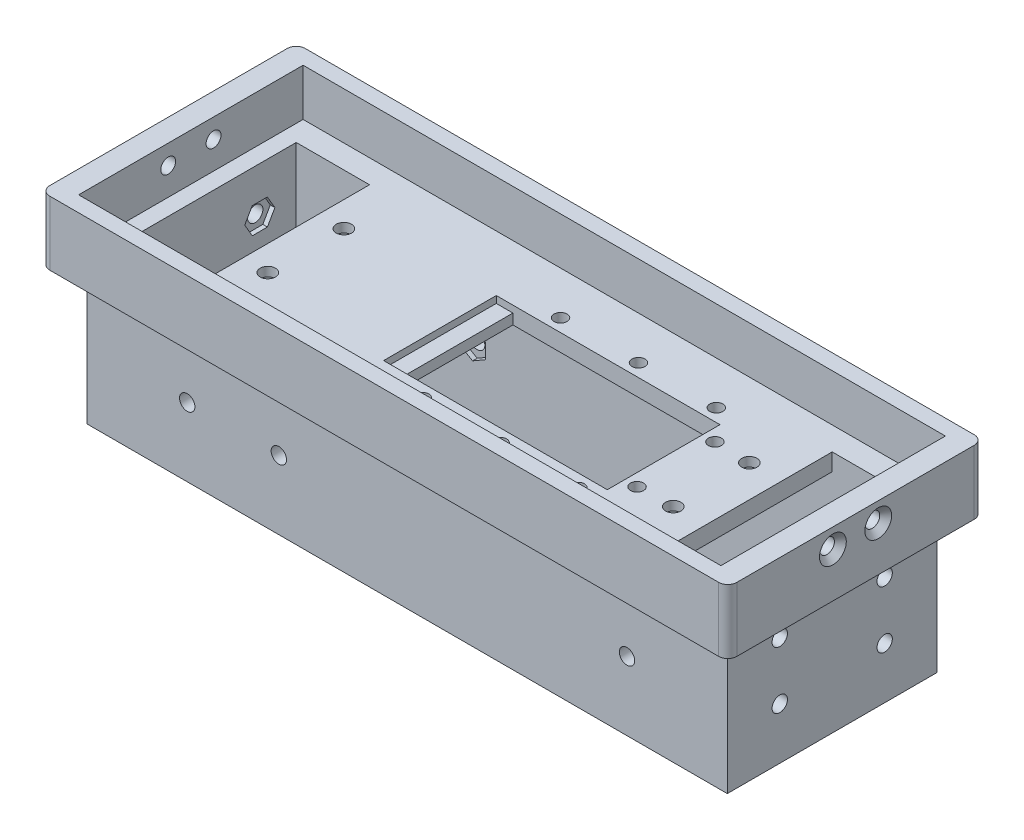
SolidWorks part; units mm, degrees
ref_plane "前视基准面" through (0, 0, 0) normal (0, 0, 1) x (1, 0, 0)
ref_plane "上视基准面" through (0, 0, 0) normal (0, 1, 0) x (1, 0, 0)
ref_plane "右视基准面" through (0, 0, 0) normal (1, 0, 0) x (0, 0, -1)
sketch "草图1" plane through (0, 0, 0) normal (0, 1, 0) x (1, 0, 0)
  line L1 (-75, 25.9) -> (75, 25.9)
  line L2 (-75, 25.9) -> (-75, -25.9)
  line L3 (-75, -25.9) -> (75, -25.9)
  line L4 (75, 25.9) -> (75, -25.9)
  line L5 (-75, 25.9) -> (75, -25.9) construction
  line L6 (-75, -25.9) -> (75, 25.9) construction
  line L7 (-70.1, 21) -> (70.1, 21)
  line L8 (-70.1, 21) -> (-70.1, -21)
  line L9 (-70.1, -21) -> (70.1, -21)
  line L10 (70.1, 21) -> (70.1, -21)
  line L11 (-70.1, 21) -> (70.1, -21) construction
  line L12 (-70.1, -21) -> (70.1, 21) construction
  point P0 (0, 0)
  point P5 (0, 0)
  dimension "D1" = 150
  dimension "D2" = 51.8
  dimension "D3" = 4.9
  dimension "D4" = 4.9
extrude "凸台-拉伸1" add sketch "草图1" along normal blind 12
sketch "草图2" plane through (0, 0, 0) normal (0, 1, 0) x (1, 0, 0)
  line L1 (70.1, 21) -> (-70.1, 21)
  line L2 (70.1, 21) -> (70.1, -21)
  line L3 (70.1, -21) -> (-70.1, -21)
  line L4 (-70.1, 21) -> (-70.1, -21)
  line L5 (70.1, 21) -> (-70.1, -21) construction
  line L6 (70.1, -21) -> (-70.1, 21) construction
  point P0 (0, 0)
extrude "凸台-拉伸2" add sketch "草图2" along normal blind 2.25
ref_plane "基准面1" through (0, 2.25, 0) normal (0, -1, 0) x (-1, 0, 0)
sketch "草图3" plane through (0, 2.25, 0) normal (0, 1, 0) x (1, 0, 0)
  line L1 (-12.1, 12.3) -> (33.1, 12.3)
  line L2 (-12.1, 12.3) -> (-12.1, -12.3)
  line L3 (-12.1, -12.3) -> (33.1, -12.3)
  line L4 (33.1, 12.3) -> (33.1, -12.3)
  dimension "D1" = 12.1
  dimension "D2" = 12.3
  dimension "D3" = 12.3
  dimension "D4" = 45.2
extrude "切除-拉伸1" cut sketch "草图3" against normal through all contours L2 L3 L4 L1
ref_plane "基准面2" through (0, 0, 0) normal (0, -1, 0) x (-1, 0, 0)
ref_plane "基准面4" through (0, 2.25, 0) normal (0, 1, 0) x (1, 0, 0)
sketch "草图8" plane through (0, 2.25, 0) normal (0, 1, 0) x (1, 0, 0)
  line L0 (-12.1, -12.3) -> (33.1, -12.3)
  line L1 (33.1, -12.3) -> (33.1, 12.3)
  line L2 (33.1, 12.3) -> (-70.1, 12.3)
  line L3 (-70.1, 21) -> (-70.1, -21) construction
  line L4 (-70.1, 12.3) -> (-70.1, 21)
  line L5 (-70.1, 21) -> (70.1, 21)
  line L6 (70.1, 21) -> (70.1, -21)
  line L7 (70.1, -21) -> (-70.1, -21)
  line L8 (-70.1, -21) -> (-70.1, -12.3)
  line L9 (-70.1, 21) -> (-70.1, -21) construction
  line L10 (-70.1, -12.3) -> (-12.1, -12.3)
extrude "凸台-拉伸5" add sketch "草图8" along normal blind 1.5
sketch "草图9" plane through (0, 2.25, 0) normal (0, 1, 0) x (1, 0, 0)
  line L0 (-15.7293, 12.3) -> (-15.7293, -12.3)
  line L1 (-70.1, 12.3) -> (-12.1, 12.3) construction
  line L2 (-12.1, -12.3) -> (-70.1, -12.3) construction
  line L3 (-15.7293, -12.3) -> (-70.1, -12.3)
  line L4 (-70.1, -12.3) -> (-70.1, 12.3)
  line L5 (-70.1, 12.3) -> (-15.7293, 12.3)
extrude "凸台-拉伸6" add sketch "草图9" along normal blind 1.5
ref_plane "基准面5" through (0, 3.75, 0) normal (0, 1, 0) x (1, 0, 0)
sketch "草图10" plane through (0, 3.75, 0) normal (0, 1, 0) x (1, 0, 0)
  circle A0 centre (-4.5, 15.1) radius 1.425
  circle A1 centre (12.5, 15.1) radius 1.425
  circle A2 centre (29.5, 15.1) radius 1.425
  dimension "D1" = 2.85
  dimension "D2" = 2.85
  dimension "D3" = 2.85
extrude "Screw_holes_for_connectng_the_servo" cut sketch "草图10" against normal through all
mirror "Screw_holes_for_connectng_the_servo(2)" about plane through (0, 0, 0) normal (0, 0, 1) of "Screw_holes_for_connectng_the_servo"
ref_plane "基准面7" through (0, 0, 0) normal (0, -1, 0) x (-1, 0, 0)
sketch "草图12" plane through (0, 0, 0) normal (0, -1, 0) x (-1, 0, 0)
  line L0 (75, 25.9) -> (75, -25.9) construction
  line L1 (-70, 22.9) -> (70, 22.9)
  line L2 (-70, 22.9) -> (-70, -22.9)
  line L3 (-70, -22.9) -> (70, -22.9)
  line L4 (70, 22.9) -> (70, -22.9)
  line L5 (-70, 22.9) -> (70, -22.9) construction
  line L6 (-70, -22.9) -> (70, 22.9) construction
  line L7 (-75, 25.9) -> (75, 25.9) construction
  line L9 (-66.5, 19.4) -> (66.5, 19.4)
  line L10 (-66.5, 19.4) -> (-66.5, -19.4)
  line L11 (-66.5, -19.4) -> (66.5, -19.4)
  line L12 (66.5, 19.4) -> (66.5, -19.4)
  line L13 (-66.5, 19.4) -> (66.5, -19.4) construction
  line L14 (-66.5, -19.4) -> (66.5, 19.4) construction
  point P0 (0, 0)
  point P10 (0, 0)
  dimension "D1" = 5
  dimension "D2" = 3
  dimension "D3" = 3.5
  dimension "D4" = 3.5
extrude "凸台-拉伸9" add sketch "草图12" along normal blind 25
ref_plane "基准面8" through (0, 0, 0) normal (0, -1, 0) x (-1, 0, 0)
sketch "草图16" plane through (0, 0, 0) normal (0, -1, 0) x (-1, 0, 0)
  line L0 (-66.5, 19.4) -> (-66.5, -19.9)
  line L1 (-66.5, 19.4) -> (-66.5, -19.4) construction
  line L2 (-66.5, 19.4) -> (-66.5, -19.4) construction
  line L3 (-66.5, -19.9) -> (-50.5, -19.4)
  line L4 (-66.5, -19.4) -> (66.5, -19.4) construction
  line L5 (-50.5, -19.4) -> (-50.5, 19.4)
  line L6 (66.5, 19.4) -> (-66.5, 19.4) construction
  line L7 (-50.5, 19.4) -> (-66.5, 19.4)
  line L8 (66.5, 19.4) -> (50.5, 19.4)
  line L9 (50.5, 19.4) -> (50.5, -19.4)
  line L10 (50.5, -19.4) -> (66.5, -19.4)
  line L11 (66.5, -19.4) -> (66.5, 19.4)
  dimension "D1" = 16
  dimension "D2" = 16
extrude "切除-拉伸4" cut sketch "草图16" against normal through all
ref_plane "基准面9" through (75, 0, 0) normal (1, 0, 0) x (0, 0, -1)
sketch "草图18" plane through (75, 0, 0) normal (1, 0, 0) x (0, 0, -1)
  line L0 (0, 12) -> (0, 5.5)
  line L1 (-25.9, 12) -> (25.9, 12) construction
  line L2 (0, 8.75) -> (-4.95, 8.75)
  line L3 (0, 8.75) -> (4.95, 8.75)
  circle A0 centre (4.95, 8.75) radius 1.6
  circle A1 centre (-4.95, 8.75) radius 1.6
  dimension "D1" = 4.95
  dimension "D2" = 4.95
extrude "切除-拉伸5" [suppressed] cut sketch "草图18" against normal through all contours A1 | A0
ref_plane "基准面11" through (0, 0, 25.9) normal (0, 0, 1) x (1, 0, 0)
ref_plane "基准面12" through (0, 0, -25.9) normal (0, 0, -1) x (-1, 0, 0)
sketch "草图21" plane through (0, 0, 25.9) normal (0, 0, 1) x (1, 0, 0)
  line L0 (75, 12) -> (75, 5.5)
  line L1 (75, 12) -> (75, 0) construction
  line L2 (75, 5.5) -> (75, 8.75)
  line L3 (75, 8.75) -> (72, 8.75)
  line L4 (72, 8.75) -> (62, 8.75)
  line L5 (62, 8.75) -> (52, 8.75)
  line L6 (52, 8.75) -> (42, 8.75)
  line L7 (42, 12) -> (42, 5.5)
  line L8 (-75, 12) -> (75, 12) construction
  line L9 (42, 5.5) -> (52, 12)
  line L10 (52, 12) -> (52, 5.5)
  line L11 (52, 5.5) -> (62, 12)
  line L12 (62, 12) -> (62, 5.5)
  line L13 (62, 5.5) -> (72, 5.5)
  line L14 (72, 5.5) -> (72, 12)
  line L15 (72, 12) -> (62, 5.5)
  circle A1 centre (57, 8.75) radius 1.6
  circle A2 centre (67, 8.75) radius 1.6
sketch "草图22" plane through (0, 0, -25.9) normal (0, 0, -1) x (-1, 0, 0)
  line L0 (75, 12) -> (75, 5.5)
  line L1 (75, 12) -> (75, 0) construction
  line L2 (75, 5.5) -> (75, 8.75)
  line L3 (75, 8.75) -> (72, 8.75)
  line L4 (72, 8.75) -> (62, 8.75)
  line L5 (62, 8.75) -> (52, 8.75)
  line L7 (72, 12) -> (72, 5.5)
  line L8 (-75, 12) -> (75, 12) construction
  line L9 (72, 5.5) -> (62, 12)
  line L10 (62, 12) -> (62, 5.5)
  line L11 (62, 5.5) -> (52, 12)
  circle A4 centre (57, 8.75) radius 1.6
  circle A5 centre (67, 8.75) radius 1.6
extrude "切除-拉伸12" [suppressed] cut sketch "草图21" against normal blind 5 contours A1 | A2
extrude "切除-拉伸13" [suppressed] cut sketch "草图22" along normal blind 2 and the other way blind 5 contours A4 | A5
ref_plane "基准面13" through (70, 0, 0) normal (1, 0, 0) x (0, 0, -1)
sketch "草图23" plane through (70, 0, 0) normal (1, 0, 0) x (0, 0, -1)
  line L0 (22.9, -25) -> (-22.9, 0)
  line L1 (-22.9, 0) -> (-22.9, -25)
  line L2 (-22.9, -25) -> (22.9, 0)
  line L3 (22.9, 0) -> (22.9, -12.5)
  line L4 (22.9, -25) -> (22.9, 0) construction
  line L5 (22.9, -12.5) -> (-22.9, -12.5)
  line L6 (-22.9, -12.5) -> (0, 0)
  line L7 (0, 0) -> (0, -25)
  line L8 (22.9, -25) -> (-22.9, -25) construction
  line L9 (0, -25) -> (22.9, -12.5)
  line L10 (22.9, -12.5) -> (0, 0)
  line L11 (-22.9, -12.5) -> (0, -25)
  circle A0 centre (-11.45, -6.25) radius 1.675
  circle A1 centre (11.45, -6.25) radius 1.675
  circle A2 centre (11.45, -18.75) radius 1.675
  circle A3 centre (-11.45, -18.75) radius 1.675
  dimension "D1" = 3.35
  dimension "D2" = 3.35
  dimension "D3" = 3.35
  dimension "D4" = 3.35
extrude "切除-拉伸14" cut sketch "草图23" against normal through all contours A0 | A3 | A1 | A2
ref_plane "基准面14" through (0, 0, -22.9) normal (0, 0, -1) x (-1, 0, 0)
sketch "草图24" plane through (0, 0, -22.9) normal (0, 0, -1) x (-1, 0, 0)
  line L0 (70, -12.5) -> (24, -12.5)
  line L1 (70, -25) -> (70, 0) construction
  line L2 (24, -12.5) -> (-24, -12.5)
  line L3 (-24, -12.5) -> (-70, -12.5)
  line L4 (-70, 13.75) -> (-70, -13.75) construction
  line L6 (70, -25) -> (-70, -25) construction
  line L7 (-70, -25) -> (-24, 0)
  line L8 (-75, 0) -> (75, 0) construction
  line L9 (-24, 0) -> (24, -25)
  line L10 (24, -25) -> (70, 0)
  circle A2 centre (47, -12.5) radius 2.075
  circle A3 centre (-47, -12.5) radius 2.075
  dimension "D1" = 4.15
  dimension "D2" = 4.15
sketch "草图26" plane through (0, 3.75, 0) normal (0, 1, 0) x (1, 0, 0)
  line L0 (-70.1, -21) -> (-70.1, 21)
  dimension "D1" = 42
ref_plane "基准面15" through (0, 0, -21) normal (0, 0, 1) x (1, 0, 0)
ref_plane "基准面16" through (0, 0, 21) normal (0, 0, -1) x (-1, 0, 0)
ref_plane "基准面17" through (-70.1, 0, 0) normal (1, 0, 0) x (0, 0, -1)
ref_plane "基准面18" through (50.5, 0, 0) normal (1, 0, 0) x (0, 0, -1)
ref_plane "基准面19" through (0, 0, 0) normal (0, -1, 0) x (-1, 0, 0)
sketch "草图49" plane through (0, -25, 0) normal (0, -1, 0) x (-1, 0, 0)
  line L1 (66.5, -19.4) -> (-66.5, -19.4)
  line L2 (66.5, -19.4) -> (66.5, 19.4)
  line L3 (66.5, 19.4) -> (-66.5, 19.4)
  line L4 (-66.5, -19.4) -> (-66.5, 19.4)
  line L5 (70, -22.9) -> (-70, -22.9)
  line L6 (70, -22.9) -> (70, 22.9)
  line L7 (70, 22.9) -> (-70, 22.9)
  line L8 (-70, -22.9) -> (-70, 22.9)
extrude "凸台-拉伸13" add sketch "草图49" along normal blind 5
sketch "草图53" plane through (70, 0, 0) normal (1, 0, 0) x (0, 0, -1)
  line L1 (-22.9, 0) -> (22.9, 0)
  line L2 (-22.9, 0) -> (-22.9, -30)
  line L3 (-22.9, -30) -> (22.9, -30)
  line L4 (22.9, 0) -> (22.9, -30)
  circle A0 centre (-11.45, -6.25) radius 1.6
  circle A1 centre (-11.45, -18.75) radius 1.6
  circle A2 centre (11.45, -18.75) radius 1.6
  circle A3 centre (11.45, -6.25) radius 1.6
extrude "切除-拉伸19" cut sketch "草图53" against normal blind 0.1
mirror "镜向7" about plane through (0, 0, 0) normal (1, 0, 0) of "切除-拉伸19"
ref_plane "基准面20" through (0, 0, -22.9) normal (0, 0, -1) x (-1, 0, 0)
sketch "草图59" plane through (0, 0, -22.9) normal (0, 0, -1) x (-1, 0, 0)
  line L0 (-69.9, 0) -> (-69.9, -15)
  line L1 (-69.9, -15) -> (69.9, -15)
  line L2 (-69.9, -30) -> (-69.9, 0) construction
  line L3 (-69.9, -15) -> (-48, -15)
  line L4 (69.9, 0) -> (69.9, -15)
  line L6 (69.9, -30) -> (69.9, 0) construction
  line L7 (69.9, -15) -> (48, -15)
  line L8 (48, -15) -> (28, -15)
  circle A0 centre (-48, -15) radius 1.675
  circle A1 centre (28, -15) radius 1.675
  circle A2 centre (48, -15) radius 1.675
  point P2 (0, -15)
  dimension "D1" = 3.35
  dimension "D2" = 3.35
  dimension "D3" = 3.35
  dimension "D4" = 28
  dimension "D5" = 20
  dimension "D6" = 48
extrude "切除-拉伸20" cut sketch "草图59" against normal through all contours A0 | A1 | A2
ref_plane "基准面22" through (-50.5, 0, 0) normal (-1, 0, 0) x (0, 0, 1)
ref_plane "基准面23" through (0, 3.75, 0) normal (0, 1, 0) x (1, 0, 0)
sketch "草图66" plane through (0, 3.75, 0) normal (0, 1, 0) x (1, 0, 0)
  line L0 (29.5, -15.1) -> (43.5, -15.1)
  line L1 (33.1, -12.3) -> (43.5, -12.3)
  line L2 (43.5, -12.3) -> (43.5, -8.3)
  line L3 (33.1, 12.3) -> (43.5, 12.3)
  line L4 (43.5, 12.3) -> (43.5, 8.3)
  line L5 (0, 0) -> (43.5, 0)
  line L6 (0, 0) -> (-45, 0)
  line L7 (-45, 0) -> (-45, 8.3)
  line L8 (-45, 0) -> (-45, -8.3)
  circle A0 centre (43.5, -8.3) radius 1.675
  circle A1 centre (43.5, 8.3) radius 1.675
  circle A2 centre (-45, 8.3) radius 1.675
  circle A3 centre (-45, -8.3) radius 1.675
  dimension "D4" = 43.5
  dimension "D1" = 14
  dimension "D2" = 4
  dimension "D3" = 4
  dimension "D5" = 45
  dimension "D6" = 8.3
extrude "切除-拉伸21" cut sketch "草图66" against normal blind 20 contours A2 | A3 | A1 | A0
ref_plane "基准面24" through (0, 0, -25.9) normal (0, 0, -1) x (-1, 0, 0)
sketch "草图67" plane through (0, 0, -25.9) normal (0, 0, -1) x (-1, 0, 0)
  line L1 (-75, 12) -> (75, 12)
  line L2 (-75, 12) -> (-75, 0)
  line L3 (-75, 0) -> (75, 0)
  line L4 (75, 12) -> (75, 0)
extrude "凸台-拉伸15" add sketch "草图67" along normal blind 2
mirror "镜向10" about plane through (0, 0, 0) normal (0, 0, 1) of "凸台-拉伸15"
sketch "草图69" plane through (0, 3.75, 0) normal (0, 1, 0) x (1, 0, 0)
  line L0 (29.5, 15.1) -> (35.8, 15.1)
  line L2 (29.5, -15.1) -> (35.8, -15.1)
  circle A0 centre (35.8, 8.5) radius 1.425
  circle A1 centre (35.8, -8.5) radius 1.425
extrude "切除-拉伸22" cut sketch "草图69" against normal up to next contours A0 | A1 region at (35.8, 3.75, -8.5) region at (35.8, 3.75, 8.5)
sketch "草图71" plane through (0, 0, 0) normal (0, -1, 0) x (-1, 0, 0)
  line L0 (-40.65, -6.6546) -> (-40.65, -2.614)
  line L1 (-43.5, -5.0091) -> (-46.35, -6.6546)
  line L2 (-46.35, -6.6546) -> (-46.35, -9.9454)
  line L3 (-46.35, -9.9454) -> (-43.5, -11.5909)
  line L4 (-43.5, -11.5909) -> (-40.65, -9.9454)
  line L5 (-40.65, -9.9454) -> (-40.65, -6.6546)
  line L6 (-40.65, -6.6546) -> (-43.5, -5.0091)
  line L7 (-43.5, 11.626) -> (-46.3804, 9.963)
  line L8 (-46.3804, 9.963) -> (-46.3804, 6.637)
  line L9 (-46.3804, 6.637) -> (-43.5, 4.974)
  line L10 (-43.5, 4.974) -> (-40.6196, 6.637)
  line L11 (-40.6196, 6.637) -> (-40.6196, 9.963)
  line L12 (-40.6196, 9.963) -> (-43.5, 11.626)
  line L13 (45.0917, 11.626) -> (42.1654, 10.0425)
  line L14 (42.1654, 10.0425) -> (42.0737, 6.7164)
  line L15 (42.0737, 6.7164) -> (44.9083, 4.974)
  line L16 (44.9083, 4.974) -> (47.8346, 6.5575)
  line L17 (47.8346, 6.5575) -> (47.9263, 9.8836)
  line L18 (47.9263, 9.8836) -> (45.0917, 11.626)
  line L19 (45.0917, -4.9685) -> (42.1607, -6.5548)
  line L20 (42.1607, -6.5548) -> (42.069, -9.8863)
  line L21 (42.069, -9.8863) -> (44.9083, -11.6315)
  line L22 (44.9083, -11.6315) -> (47.8393, -10.0452)
  line L23 (47.8393, -10.0452) -> (47.931, -6.7137)
  line L24 (47.931, -6.7137) -> (45.0917, -4.9685)
  line L26 (-40.65, -9.9454) -> (-40.65, -13.9454)
  circle A0 centre (-43.5, -8.3) radius 2.85 construction
  circle A1 centre (-43.5, 8.3) radius 2.8804 construction
  circle A2 centre (45, 8.3) radius 2.8815 construction
  circle A3 centre (45, -8.3) radius 2.8863 construction
  circle A4 centre (-43.5, -8.3) radius 1.675
  circle A5 centre (-43.5, 8.3) radius 1.675
  circle A6 centre (45, -8.3) radius 1.675
  circle A7 centre (45, 8.3) radius 1.675
  point P28 (42.1196, 8.3795)
  circle M12 centre (-43.5, -8.3) radius 1.675
  dimension "D4" = 5.7
  dimension "D1" = 5.7609
  dimension "D2" = 5.7631
  dimension "D3" = 5.7725
sketch "草图74" plane through (0, 0, 0) normal (0, -1, 0) x (-1, 0, 0)
  line L1 (45, -5.0091) -> (42.15, -6.6546)
  line L2 (42.15, -6.6546) -> (42.15, -9.9454)
  line L3 (42.15, -9.9454) -> (45, -11.5909)
  line L4 (45, -11.5909) -> (47.85, -9.9454)
  line L5 (47.85, -9.9454) -> (47.85, -6.6546)
  line L6 (47.85, -6.6546) -> (45, -5.0091)
  line L8 (40, -5.4132) -> (40, -11.1868)
  line L11 (50, -11.1868) -> (50, -5.4132)
  line L13 (45, -14.0735) -> (50, -11.1868) [skipped]
  line L14 (50, -5.4132) -> (45, -2.5265) [skipped]
  line L15 (40, -11.1868) -> (45, -14.0735) [skipped]
  line L16 (45, -2.5265) -> (40, -5.4132) [skipped]
  circle A0 centre (45, -8.3) radius 2.85 construction
  circle A1 centre (45, -8.3) radius 5 construction
  circle A2 centre (45, -8.3) radius 1.675
  circle M30 centre (45, -8.3) radius 1.675
  dimension "D1" = 5.7
  dimension "D2" = 10
sketch "草图77" plane through (0, 0, -21) normal (0, 0, 1) x (1, 0, 0)
  line L0 (-70.1, 12) -> (-70.1, 3.75)
  line L1 (-70.1, 3.75) -> (70.1, 3.75)
  line L2 (70.1, 3.75) -> (70.1, 12)
  line L3 (70.1, 12) -> (-70.1, 12)
extrude "切除-拉伸23" cut sketch "草图77" against normal blind 3.5
mirror "镜向13" about plane through (0, 0, 0) normal (0, 0, 1) of "切除-拉伸23"
chamfer "倒角1" [suppressed] distance 1.3 angle 45
chamfer "倒角2" [suppressed] distance 1.3 angle 45
sketch "草图82" plane through (66.5, 0, 0) normal (-1, 0, 0) x (0, 0, 1)
  line L1 (-9.8171, -9.1072) -> (-8.1591, -6.2645)
  line L2 (-8.1591, -6.2645) -> (-9.792, -3.4073)
  line L3 (-9.792, -3.4073) -> (-13.0829, -3.3928)
  line L4 (-13.0829, -3.3928) -> (-14.7409, -6.2355)
  line L5 (-14.7409, -6.2355) -> (-13.108, -9.0927)
  line L6 (-13.108, -9.0927) -> (-9.8171, -9.1072)
  line L7 (13.0829, -9.1072) -> (14.7409, -6.2645)
  line L8 (14.7409, -6.2645) -> (13.108, -3.4073)
  line L9 (13.108, -3.4073) -> (9.8171, -3.3928)
  line L10 (9.8171, -3.3928) -> (8.1591, -6.2355)
  line L11 (8.1591, -6.2355) -> (9.792, -9.0927)
  line L12 (9.792, -9.0927) -> (13.0829, -9.1072)
  line L13 (9.8123, -15.8955) -> (8.1591, -18.741)
  line L14 (8.1591, -18.741) -> (9.7968, -21.5955)
  line L15 (9.7968, -21.5955) -> (13.0877, -21.6045)
  line L16 (13.0877, -21.6045) -> (14.7409, -18.759)
  line L17 (14.7409, -18.759) -> (13.1032, -15.9045)
  line L18 (13.1032, -15.9045) -> (9.8123, -15.8955)
  line L19 (-9.8084, -21.6022) -> (-8.1591, -18.7545)
  line L20 (-8.1591, -18.7545) -> (-9.8007, -15.9023)
  line L21 (-9.8007, -15.9023) -> (-13.0916, -15.8978)
  line L22 (-13.0916, -15.8978) -> (-14.7409, -18.7455)
  line L23 (-14.7409, -18.7455) -> (-13.0993, -21.5977)
  line L24 (-13.0993, -21.5977) -> (-9.8084, -21.6022)
  circle A0 centre (-11.45, -6.25) radius 1.675
  circle A1 centre (-11.45, -6.25) radius 2.85 construction
  circle A2 centre (11.45, -6.25) radius 1.675
  circle A3 centre (-11.45, -18.75) radius 1.675
  circle A4 centre (11.45, -18.75) radius 1.675
  circle A5 centre (11.45, -6.25) radius 2.85 construction
  circle A6 centre (11.45, -18.75) radius 2.85 construction
  circle A7 centre (-11.45, -18.75) radius 2.85 construction
  dimension "D1" = 5.7
  dimension "D2" = 5.7
  dimension "D3" = 5.7
  dimension "D4" = 5.7
extrude "切除-拉伸24" cut sketch "草图82" against normal blind 1
mirror "镜向14" about plane through (0, 0, 0) normal (1, 0, 0) of "切除-拉伸24"
sketch "草图83" plane through (0, 0, 19.4) normal (0, 0, -1) x (-1, 0, 0)
  line L1 (48, -11.7091) -> (45.15, -13.3546)
  line L2 (45.15, -13.3546) -> (45.15, -16.6454)
  line L3 (45.15, -16.6454) -> (48, -18.2909)
  line L4 (48, -18.2909) -> (50.85, -16.6454)
  line L5 (50.85, -16.6454) -> (50.85, -13.3546)
  line L6 (50.85, -13.3546) -> (48, -11.7091)
  line L7 (28, -11.7091) -> (25.15, -13.3546)
  line L8 (25.15, -13.3546) -> (25.15, -16.6454)
  line L9 (25.15, -16.6454) -> (28, -18.2909)
  line L10 (28, -18.2909) -> (30.85, -16.6454)
  line L11 (30.85, -16.6454) -> (30.85, -13.3546)
  line L12 (30.85, -13.3546) -> (28, -11.7091)
  line L13 (-48, -11.7091) -> (-50.85, -13.3546)
  line L14 (-50.85, -13.3546) -> (-50.85, -16.6454)
  line L15 (-50.85, -16.6454) -> (-48, -18.2909)
  line L16 (-48, -18.2909) -> (-45.15, -16.6454)
  line L17 (-45.15, -16.6454) -> (-45.15, -13.3546)
  line L18 (-45.15, -13.3546) -> (-48, -11.7091)
  circle A0 centre (48, -15) radius 2.85 construction
  circle A1 centre (48, -15) radius 1.675
  circle A2 centre (28, -15) radius 1.675
  circle A3 centre (28, -15) radius 2.85 construction
  circle A4 centre (-48, -15) radius 2.85 construction
  circle A5 centre (-48, -15) radius 1.675
  dimension "D1" = 5.7
  dimension "D2" = 5.7
  dimension "D3" = 5.7
extrude "切除-拉伸25" cut sketch "草图83" against normal blind 1
mirror "镜向15" about plane through (0, 0, 0) normal (0, 0, 1) of "切除-拉伸25"
fillet "圆角1" [suppressed] radius 2
sketch "草图93" plane through (0, 12, 0) normal (0, 1, 0) x (1, 0, 0)
  line L1 (70.1, -24.5) -> (-70.1, -24.5)
  line L2 (70.1, -24.5) -> (70.1, 24.5)
  line L3 (70.1, 24.5) -> (-70.1, 24.5)
  line L4 (-70.1, -24.5) -> (-70.1, 24.5)
  line L5 (75, -27.9) -> (-75, -27.9)
  line L6 (75, -27.9) -> (75, 27.9)
  line L7 (75, 27.9) -> (-75, 27.9)
  line L8 (-75, -27.9) -> (-75, 27.9)
extrude "凸台-拉伸19" add sketch "草图93" along normal blind 2
sketch "草图95" plane through (75, 0, 0) normal (1, 0, 0) x (0, 0, -1)
  line L0 (0, 14) -> (0, 9.75)
  line L1 (-27.9, 14) -> (27.9, 14) construction
  line L2 (0, 9.75) -> (-4.95, 9.75)
  line L3 (0, 9.75) -> (4.95, 9.75)
  circle A0 centre (4.95, 9.75) radius 1.625
  circle A1 centre (-4.95, 9.75) radius 1.625
extrude "切除-拉伸27" cut sketch "草图95" against normal through all contours A0 | A1 region at (75, 9.75, 6.529) region at (75, 11.329, -4.95)
chamfer "倒角4" distance 1.3 angle 45 4 edges at (-75, 9.75, -6.575) (-75, 9.75, 3.325) (75, 9.75, 3.325) (75, 9.75, -6.575)
extrude "切除-拉伸28" cut sketch "草图74" against normal blind 1.75 contours L5 L6 L1 L2 L3 L4 M30 region at (-46.3815, 0, 5.9072)
extrude "切除-拉伸29" cut sketch "草图71" against normal blind 1.75 contours L5 L6 L1 L2 L3 L4 M12 region at (42.1185, 0, 5.9072)
mirror "镜向16" about plane through (0, 0, 0) normal (0, 0, 1) of "切除-拉伸29", "切除-拉伸28"
fillet "圆角2" radius 2 4 edges at (-75, 7, -27.9) (-75, 7, 27.9) (75, 7, 27.9) (75, 7, -27.9)
